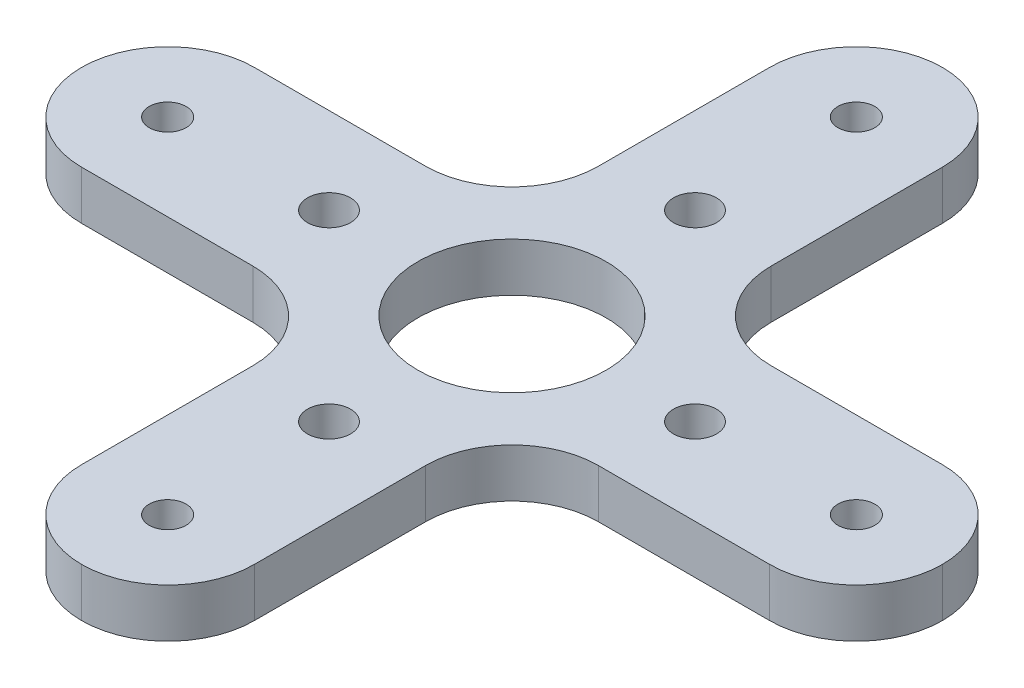
SolidWorks part; units mm, degrees
ref_plane "Front Plane" through (0, 0, 0) normal (0, 0, 1) x (1, 0, 0)
ref_plane "Top Plane" through (0, 0, 0) normal (0, 1, 0) x (1, 0, 0)
ref_plane "Right Plane" through (0, 0, 0) normal (1, 0, 0) x (0, 0, -1)
sketch "Sketch1" plane through (0, 0, 0) normal (0, 1, 0) x (1, 0, 0)
  line L0 (35, 7.025) -> (7.025, 7.025)
  line L1 (7.025, 7.025) -> (7.025, 35)
  line L2 (-35, -7.025) -> (-7.025, -7.025)
  line L3 (-7.025, -7.025) -> (-7.025, -35)
  line L4 (35, -7.025) -> (7.025, -7.025)
  line L5 (7.025, -7.025) -> (7.025, -35)
  line L6 (-35, 7.025) -> (-35, -7.025)
  line L7 (-7.025, -35) -> (7.025, -35)
  line L9 (35, -7.025) -> (35, 7.025)
  line L10 (-35, 7.025) -> (-7.025, 7.025)
  line L11 (-7.025, 7.025) -> (-7.025, 35)
  line L14 (-7.025, 35) -> (7.025, 35)
  dimension "D1" = 27.975
  dimension "D2" = 14.05
  dimension "D3" = 14.05
  dimension "D7" = 27.975
sketch "Sketch3" plane through (0, 0, 0) normal (0, 1, 0) x (1, 0, 0)
  line L0 (-38.0499, 0) -> (37.9537, 0) construction
  line L1 (0, -39.2305) -> (0, 40.7512) construction
  circle A0 centre (0, 0) radius 7.655
  circle A1 centre (-14.88, 0) radius 1.75
  circle A2 centre (-28, 0) radius 1.5
  circle A3 centre (28, 0) radius 1.5
  circle A4 centre (14.88, 0) radius 1.75
  circle A5 centre (0, 14.88) radius 1.75
  circle A6 centre (0, 28) radius 1.5
  circle A7 centre (0, -28) radius 1.5
  circle A8 centre (0, -14.88) radius 1.75
  point P21 (-43.4797, -16.9794)
  dimension "D1" = 15.31
  dimension "D2" = 3.5
  dimension "D3" = 3
  dimension "D6" = 3
  dimension "D7" = 3.5
  dimension "D4" = 14.88
  dimension "D5" = 28
  dimension "D8" = 14.88
  dimension "D9" = 28
extrude "Boss-Extrude1" add sketch "Sketch1" along normal blind 3.96
extrude "Cut-Extrude1" cut sketch "Sketch3" along normal through all
fillet "Fillet2" radius 7.025 12 edges at (7.025, 1.98, 7.025) (7.025, 1.98, -7.025) (-7.025, 1.98, -7.025) (-7.025, 1.98, 7.025) (35, 1.98, -7.025) (35, 1.98, 7.025) (7.025, 1.98, 35) (-7.025, 1.98, 35) (-35, 1.98, 7.025) (-35, 1.98, -7.025) (7.025, 1.98, -35) (-7.025, 1.98, -35)
